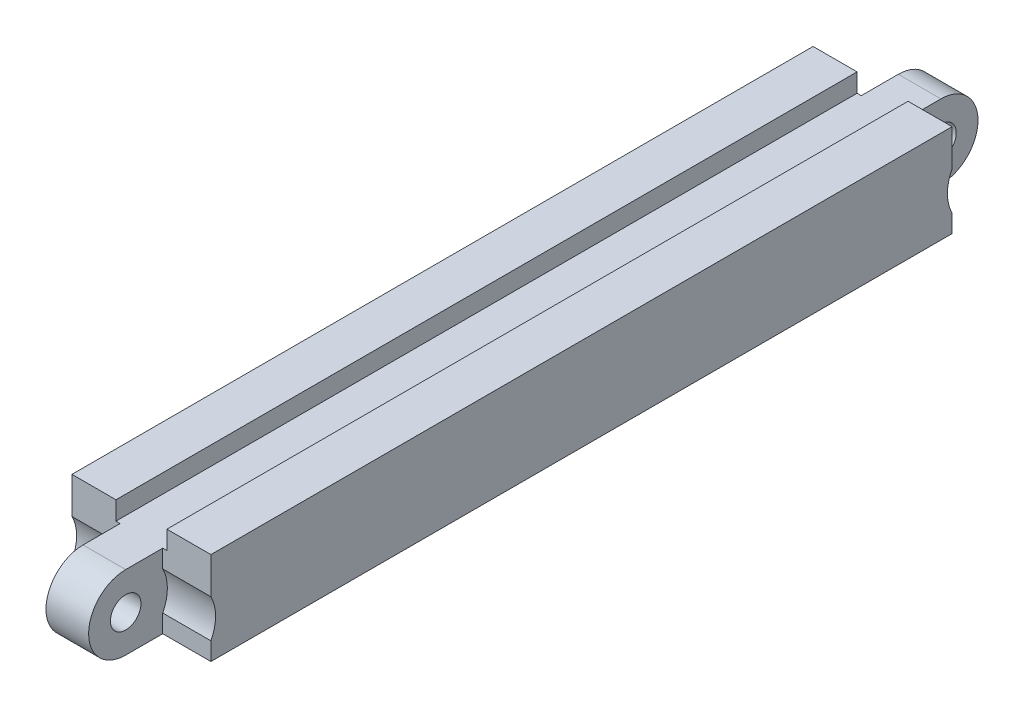
SolidWorks part; units mm, degrees
ref_plane "Front Plane" through (0, 0, 0) normal (0, 0, 1) x (1, 0, 0)
ref_plane "Top Plane" through (0, 0, 0) normal (0, 1, 0) x (1, 0, 0)
ref_plane "Right Plane" through (0, 0, 0) normal (1, 0, 0) x (0, 0, -1)
sketch "Sketch1" plane through (0, 0, 0) normal (1, 0, 0) x (0, 0, -1)
  line L0 (0, 4) -> (40, 4)
  line L1 (40, 4) -> (40, -4)
  line L2 (40, -4) -> (0, -4)
  line L3 (0, -4) -> (0, 4)
  line L4 (44, 4) -> (40, 4)
  line L5 (44, -4) -> (40, -4)
  line L6 (0, 6) -> (40, 6)
  line L7 (36, 6) -> (36, 4)
  line L9 (40, 6) -> (40, 4)
  line L10 (0, 6) -> (0, 4)
  line L11 (36, 4) -> (36, -4)
  line L13 (40, -6) -> (0, -6) construction
  line L14 (40, -6) -> (45.2386, -6) construction
  line L15 (40, 6) -> (45.2386, 6) construction
  line L16 (40, 4) -> (45.014, 4) construction
  line L17 (40, -4) -> (45.014, -4) construction
  arc A0 (44, -4) -> (44, 4) centre (44, 0) ccw
  circle A1 centre (44, 0) radius 1.65
  arc A3 (45.2386, 6) -> (45.2386, -6) centre (44, 0) cw construction
  arc A4 (45.014, 4) -> (45.014, -4) centre (44, 0) cw construction
  point P9 (0, 0)
  point P22 (40, 0)
  dimension "D1" = 3.3
  dimension "D2" = 8
  dimension "D7" = 4
  dimension "D3" = 40
  dimension "D4" = 4
  dimension "D6" = 4
  dimension "D5" = 2
extrude "Boss-Extrude1" add sketch "Sketch1" along normal blind 7.5 contours L3 L2 L1 L0 | L0 L11 L2 L1 region at (0, 0, -18) region at (0, 0, -38)
extrude "Boss-Extrude2" add sketch "Sketch1<5>" along normal up to surface (7.5 mm away) from offset 2.75 contours L3 L2 L1 L0 | L6 L10 L0 L9 | L0 L11 L2 L1 | L9 L6 L7 L0 region at (0, 5, -18) region at (0, 0, -18) region at (0, 5, -38) region at (0, 0, -38) up to face at (7.5, 0, -20)
sketch "Sketch1<5>" plane through (0, 0, 0) normal (1, 0, 0) x (0, 0, -1) same geometry as "Sketch1"
extrude "Boss-Extrude3" add sketch "Sketch1<7>" along normal blind 2.3 contours A1 L1 | L0 L11 L2 L1 region at (0, 0, -38) region at (0, 3.8869, -42)
sketch "Sketch1<7>" plane through (0, 0, 0) normal (1, 0, 0) x (0, 0, -1) same geometry as "Sketch1"
sketch "Sketch3" plane through (0, 0, 0) normal (1, 0, 0) x (0, 0, -1)
  circle A0 centre (44, 0) radius 4.5
  dimension "D1" = 9
extrude "Cut-Extrude3" cut sketch "Sketch3" along normal through all from surface contours A0 | A0 region at (0, 0, -44) starting at face at (2.3, 0, -45.65)
mirror "Mirror1" about plane through (0, 0, 0) normal (1, 0, 0) of bodies 108 102
mirror "Mirror2" about plane through (0, 0, 0) normal (0, 0, 1) of bodies 103
